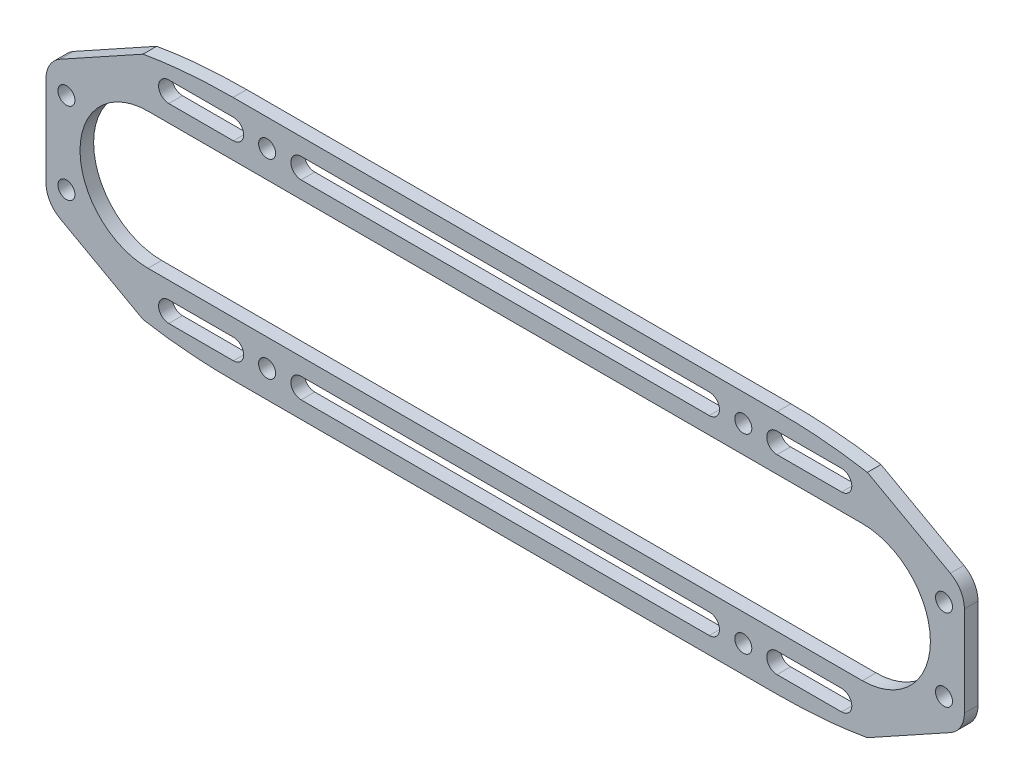
SolidWorks part; units mm, degrees
material "Thornel Mat VMA"
ref_plane "前视基准面" through (0, 0, 0) normal (0, 0, 1) x (1, 0, 0)
ref_plane "上视基准面" through (0, 0, 0) normal (0, 1, 0) x (1, 0, 0)
ref_plane "右视基准面" through (0, 0, 0) normal (1, 0, 0) x (0, 0, -1)
sketch "草图1" plane through (0, 0, 0) normal (0, 0, 1) x (1, 0, 0)
  line L1 (67.5, 9) -> (-67.5, 9)
  line L2 (67.5, 9) -> (67.5, -9)
  line L3 (67.5, -9) -> (-67.5, -9)
  line L4 (-67.5, 9) -> (-67.5, -9)
  line L5 (67.5, 9) -> (-67.5, -9) construction
  line L6 (67.5, -9) -> (-67.5, 9) construction
  point P0 (0, 0)
  dimension "D1" = 135
  dimension "D2" = 18
extrude "凸台-拉伸1" add sketch "草图1" along normal blind 2
sketch "草图2" plane through (0, 0, 2) normal (0, 0, 1) x (1, 0, 0)
  line L0 (40, -72) -> (40, 18) construction
  line L1 (-40, 18) -> (40, 18)
  line L2 (67.5, 9) -> (-67.5, 9) construction
  line L3 (67.5, -9) -> (67.5, 9) construction
  line L4 (-67.5, 0) -> (0, 0) construction
  line L5 (-67.5, 9) -> (-67.5, -9) construction
  line L6 (-67.5, 9) -> (-67.5, -9)
  line L7 (67.5, 9) -> (67.5, -9)
  line L8 (-40, -18) -> (40, -18)
  ellipse E0 centre (-40, 9) end of major axis (-67.5, 9) minor radius 9 (-40, 18) -> (-67.5, 9) ccw
  ellipse E1 centre (40, 9) end of major axis (12.5, 9) minor radius 9 (67.5, 9) -> (40, 18) ccw
  ellipse E2 centre (40, -9) end of major axis (12.5, -9) minor radius 9 (40, -18) -> (67.5, -9) ccw
  ellipse E3 centre (-40, -9) end of major axis (-67.5, -9) minor radius 9 (-67.5, -9) -> (-40, -18) ccw
  point P49 (0, 0)
extrude "凸台-拉伸2" add sketch "草图2" against normal blind 2
sketch "草图3" plane through (0, 0, 2) normal (0, 0, 1) x (1, 0, 0)
  line L0 (-52.5, 0) -> (52.5, 0) construction
  line L1 (-52.5, 10) -> (52.5, 10)
  line L2 (-52.5, -10) -> (52.5, -10)
  line L3 (-75, 10) -> (75, 10) construction
  line L4 (0, -87.7971) -> (0, 87.7971) construction
  arc A0 (-52.5, 10) -> (-52.5, -10) centre (-52.5, 0) ccw
  arc A1 (52.5, -10) -> (52.5, 10) centre (52.5, 0) ccw
  point P3 (0, 0)
  point P10 (-47.3163, 0)
  point P11 (0, 0)
  dimension "D1" = 105
extrude "切除-拉伸1" cut sketch "草图3" against normal through all both and the other way through all
hole_wizard "孔1" positions "草图6" profile "草图7" legacy end condition through all
sketch "草图6" plane through (0, 0, 2) normal (0, 0, 1) x (1, 0, 0)
  point P0 (-64.5, 6)
  point P3 (-64.5, -6)
  point P6 (-35, 14)
  point P9 (-35, -14)
  point P12 (35, -14)
  point P15 (35, 14)
  point P18 (64.5, 6)
  point P21 (64.5, -6)
sketch "草图7" plane through (-64.5, 6, 2) normal (1, 0, 0) x (0, -1, 0)
  line L0 (0, 0) -> (0, 2)
  line L1 (0, 2) -> (1.25, 2)
  line L2 (1.25, 2) -> (1.25, 0)
  line L3 (1.25, 0) -> (0, 0)
  line L4 (0, 110) -> (0, -10) construction
  dimension "直径" = 2.5
  dimension "深度" = 2
sketch "草图8" plane through (0, 0, 2) normal (0, 0, 1) x (1, 0, 0)
  line L0 (0, 18) -> (0, 10) construction
  line L1 (30, 14) -> (-30, 14) construction
  line L2 (30, 12.5) -> (-30, 12.5)
  line L3 (40, 18) -> (-40, 18) construction
  line L4 (52.5, 10) -> (-52.5, 10) construction
  line L5 (0, -10) -> (0, -18) construction
  line L6 (-52.5, -10) -> (52.5, -10) construction
  line L7 (-40, -18) -> (40, -18) construction
  line L8 (30, 15.5) -> (-30, 15.5)
  line L9 (0, 0) -> (22.6543, 0) construction
  line L10 (30, -14) -> (-30, -14) construction
  line L11 (30, -12.5) -> (-30, -12.5)
  line L12 (30, -15.5) -> (-30, -15.5)
  line L13 (0, -18) -> (0, -10) construction
  arc A0 (30, 12.5) -> (30, 15.5) centre (30, 14) ccw
  arc A1 (-30, 15.5) -> (-30, 12.5) centre (-30, 14) ccw
  arc A2 (30, -12.5) -> (30, -15.5) centre (30, -14) cw
  arc A3 (-30, -15.5) -> (-30, -12.5) centre (-30, -14) cw
  point P14 (0, 14)
  point P24 (0, -14)
  dimension "D1" = 1.5
  dimension "D2" = 60
extrude "切除-拉伸2" cut sketch "草图8" against normal through all both and the other way through all
sketch "草图9" plane through (0, 0, 2) normal (0, 0, 1) x (1, 0, 0)
  line L0 (49.45, 14) -> (39.95, 14) construction
  line L1 (49.45, 12.5) -> (39.95, 12.5)
  line L2 (49.45, 15.5) -> (39.95, 15.5)
  line L3 (30, 14) -> (-30, 14) construction
  line L4 (30, 12.5) -> (-30, 12.5) construction
  line L5 (0, 18) -> (0, -18) construction
  line L6 (-49.45, 14) -> (-39.95, 14) construction
  line L7 (-49.45, 12.5) -> (-39.95, 12.5)
  line L8 (-49.45, 15.5) -> (-39.95, 15.5)
  line L9 (0, 0) -> (18.9861, 0) construction
  line L10 (49.45, -14) -> (39.95, -14) construction
  line L11 (49.45, -12.5) -> (39.95, -12.5)
  line L12 (49.45, -15.5) -> (39.95, -15.5)
  line L13 (-49.45, -14) -> (-39.95, -14) construction
  line L14 (-49.45, -12.5) -> (-39.95, -12.5)
  line L15 (-49.45, -15.5) -> (-39.95, -15.5)
  arc A0 (49.45, 12.5) -> (49.45, 15.5) centre (49.45, 14) ccw
  arc A1 (39.95, 15.5) -> (39.95, 12.5) centre (39.95, 14) ccw
  arc A2 (-49.45, 12.5) -> (-49.45, 15.5) centre (-49.45, 14) cw
  arc A3 (-39.95, 15.5) -> (-39.95, 12.5) centre (-39.95, 14) cw
  arc A4 (49.45, -12.5) -> (49.45, -15.5) centre (49.45, -14) cw
  arc A5 (39.95, -15.5) -> (39.95, -12.5) centre (39.95, -14) cw
  arc A6 (-49.45, -12.5) -> (-49.45, -15.5) centre (-49.45, -14) ccw
  arc A7 (-39.95, -15.5) -> (-39.95, -12.5) centre (-39.95, -14) ccw
  point P2 (44.7, 14)
  point P18 (-44.7, 14)
  point P28 (44.7, -14)
  point P35 (-44.7, -14)
  dimension "D1" = 9.5
  dimension "D2" = 14.7
extrude "切除-拉伸3" cut sketch "草图9" against normal through all both and the other way through all
sketch "草图11" plane through (0, 0, 2) normal (0, 0, 1) x (1, 0, 0)
  line L0 (-65.4363, 10.1417) -> (-53.2413, 16.888)
  line L1 (-67.5, 9) -> (-67.5, -9) construction
  line L2 (0, 18) -> (0, 0) construction
  line L3 (40, 18) -> (-40, 18) construction
  line L4 (0, 0) -> (-16.4847, 0) construction
  line L5 (71.5332, 6.6389) -> (67.5, 16.888)
  line L6 (-67.5, 16.888) -> (-53.2413, 16.888)
  line L7 (-67.5, 6.6415) -> (-67.5, 5.5918)
  line L8 (-67.5, 5.5918) -> (-71.5332, 6.6389)
  line L9 (-71.5332, 6.6389) -> (-67.5, 16.888)
  line L10 (67.5, 5.5918) -> (71.5332, 6.6389)
  line L11 (67.5, 6.6415) -> (67.5, 5.5918)
  line L12 (67.5, 16.888) -> (53.2413, 16.888)
  line L13 (65.4363, 10.1417) -> (53.2413, 16.888)
  line L14 (65.4363, -10.1417) -> (53.2413, -16.888)
  line L15 (67.5, -16.888) -> (53.2413, -16.888)
  line L16 (67.5, -6.6415) -> (67.5, -5.5918)
  line L17 (67.5, -5.5918) -> (71.5332, -6.6389)
  line L18 (-71.5332, -6.6389) -> (-67.5, -16.888)
  line L19 (-67.5, -5.5918) -> (-71.5332, -6.6389)
  line L20 (-67.5, -6.6415) -> (-67.5, -5.5918)
  line L21 (-67.5, -16.888) -> (-53.2413, -16.888)
  line L22 (71.5332, -6.6389) -> (67.5, -16.888)
  line L23 (-65.4363, -10.1417) -> (-53.2413, -16.888)
  arc A0 (-65.4363, 10.1417) -> (-67.5, 6.6415) centre (-63.5, 6.6415) ccw
  arc A1 (65.4363, 10.1417) -> (67.5, 6.6415) centre (63.5, 6.6415) cw
  arc A2 (65.4363, -10.1417) -> (67.5, -6.6415) centre (63.5, -6.6415) ccw
  arc A3 (-65.4363, -10.1417) -> (-67.5, -6.6415) centre (-63.5, -6.6415) cw
  ellipse E0 centre (-40, 9) end of major axis (-67.5, 9) minor radius 9 (-40, 18) -> (-67.5, 9) ccw construction
  point P23 (-67.5, 9)
  point P31 (67.5, 9)
  point P46 (67.5, -9)
  point P47 (-67.5, -9)
  dimension "D1" = 4
extrude "切除-拉伸4" cut sketch "草图11" against normal through all both and the other way through all
